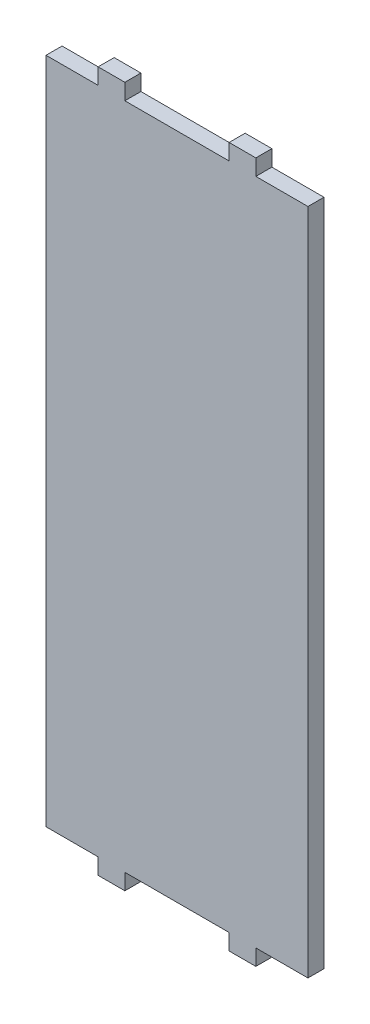
SolidWorks part; units mm, degrees
ref_plane "Plan de face" through (0, 0, 0) normal (0, 0, 1) x (1, 0, 0)
ref_plane "Plan de dessus" through (0, 0, 0) normal (0, 1, 0) x (1, 0, 0)
ref_plane "Plan de droite" through (0, 0, 0) normal (1, 0, 0) x (0, 0, -1)
sketch "Esquisse1" plane through (0, 0, 0) normal (0, 0, 1) x (1, 0, 0)
  line L0 (0, 176.8395) -> (0, -221.1538) construction
  line L1 (-49, 125) -> (49, 125)
  line L2 (-49, 125) -> (-49, -125)
  line L3 (-49, -125) -> (49, -125)
  line L4 (49, 125) -> (49, -125)
  line L5 (376.8436, 0) -> (-286.1998, 0) construction
  dimension "D1" = 250
  dimension "D2" = 98
  dimension "D3" = 49
  dimension "D4" = 125
extrude "Boss.-Extru.1" add sketch "Esquisse1" along normal blind 6
sketch "Esquisse2" plane through (0, 0, 6) normal (0, 0, 1) x (1, 0, 0)
  line L1 (-49, -125) -> (49, -125) construction
  line L2 (29.5, -125) -> (19.5, -125)
  line L3 (29.5, -125) -> (29.5, -131)
  line L4 (29.5, -131) -> (19.5, -131)
  line L6 (154.6429, 0) -> (-167.6281, 0) construction
  line L7 (19.5, -125) -> (19.5, -131)
  line L8 (-49, 125) -> (-49, -125) construction
  line L9 (-19.5, -125) -> (-29.5, -125)
  line L10 (-19.5, -125) -> (-19.5, -131)
  line L11 (-19.5, -131) -> (-29.5, -131)
  line L12 (-29.5, -125) -> (-29.5, -131)
  line L13 (-29.5, 125) -> (-29.5, 131)
  line L14 (-19.5, 131) -> (-29.5, 131)
  line L15 (-19.5, 125) -> (-19.5, 131)
  line L16 (-19.5, 125) -> (-29.5, 125)
  line L17 (19.5, 125) -> (19.5, 131)
  line L18 (29.5, 131) -> (19.5, 131)
  line L19 (29.5, 125) -> (29.5, 131)
  line L20 (29.5, 125) -> (19.5, 125)
  dimension "D1" = 6
  dimension "D2" = 6
  dimension "D3" = 10
  dimension "D4" = 10
  dimension "D5" = 19.5
  dimension "D6" = 39
extrude "Boss.-Extru.2" add sketch "Esquisse2" against normal blind 6
equation "\"D3@Esquisse1\"=\"D2@Esquisse1\"/2"
equation "\"D4@Esquisse1\"=\"D1@Esquisse1\"/2"
